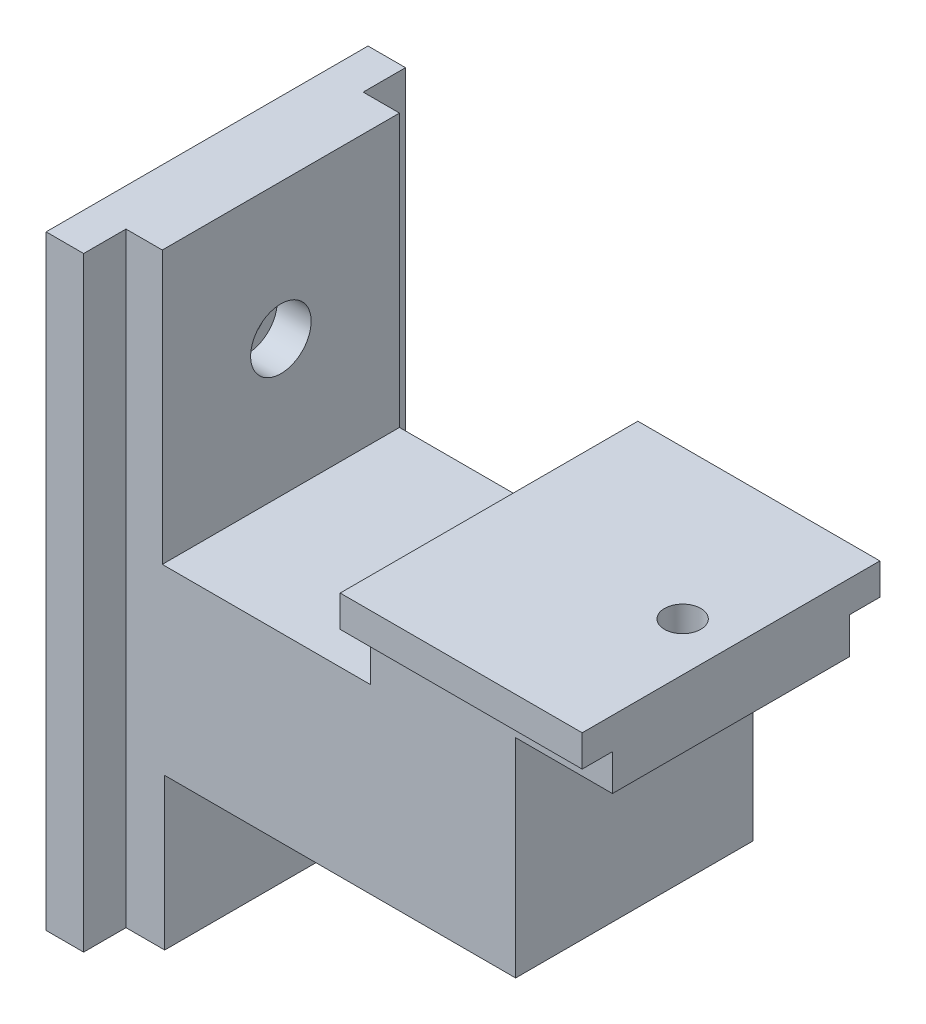
SolidWorks part; units mm, degrees
ref_plane "Front Plane" through (0, 0, 0) normal (0, 0, 1) x (1, 0, 0)
ref_plane "Top Plane" through (0, 0, 0) normal (0, 1, 0) x (1, 0, 0)
ref_plane "Right Plane" through (0, 0, 0) normal (1, 0, 0) x (0, 0, -1)
sketch "Sketch1" plane through (0, 0, 0) normal (0, 0, 1) x (1, 0, 0)
  line L0 (0, -7.5) -> (-32, -7.5)
  line L1 (-32, -7.5) -> (-32, 7.5)
  line L2 (-32, 7.5) -> (-12, 7.5)
  line L3 (-12, 7.5) -> (-12, 12.5)
  line L4 (-12, 12.5) -> (0, 12.5)
  line L5 (0, 12.5) -> (0, -7.5)
  point P8 (-32, 0)
  dimension "D1" = 15
  dimension "D2" = 20
  dimension "D3" = 12
  dimension "D4" = 20
extrude "Boss-Extrude1" add sketch "Sketch1" along normal mid plane 20
sketch "Sketch2" plane through (0, 0, 0) normal (0, 1, 0) x (1, 0, 0)
  line L0 (-32, 13.5) -> (-35.5, 13.5)
  line L1 (-35.5, 13.5) -> (-35.5, -13.5)
  line L2 (-35.5, -13.5) -> (-32, -13.5)
  line L3 (-32, -13.5) -> (-32, -10)
  line L5 (-32, 10) -> (-29, 10)
  line L6 (-12, 10) -> (-32, 10) construction
  line L7 (-29, 10) -> (-29, -10)
  line L8 (-12, -10) -> (-32, -10) construction
  line L9 (-29, -10) -> (-32, -10)
  line L10 (-32, 10) -> (-32, 13.5)
  line L11 (-32, 10) -> (-32, -10) construction
  point P11 (-35.5, 0)
  dimension "D1" = 3.5
  dimension "D2" = 27
  dimension "D3" = 3
extrude "Boss-Extrude2" add sketch "Sketch2" along normal blind 30 and the other way blind 20
sketch "Sketch3" plane through (0, 12.5, 0) normal (0, 1, 0) x (1, 0, 0)
  line L1 (8, -12.5) -> (-12, -12.5)
  line L2 (8, -12.5) -> (8, 12.5)
  line L3 (8, 12.5) -> (-12, 12.5)
  line L4 (-12, -12.5) -> (-12, 12.5)
  line L5 (8, -12.5) -> (-12, 12.5) construction
  line L6 (8, 12.5) -> (-12, -12.5) construction
  point P0 (-2, 0)
  dimension "D1" = 20
  dimension "D2" = 25
extrude "Boss-Extrude3" add sketch "Sketch3" along normal blind 3
sketch "Sketch4" plane through (0, 0, 0) normal (1, 0, 0) x (0, 0, -1)
  line L0 (-10, 12.5) -> (10, 12.5)
  line L1 (10, 12.5) -> (10, 9.5)
  line L2 (10, -7.5) -> (10, 12.5) construction
  line L3 (10, 9.5) -> (-10, 9.5)
  line L4 (-10, -7.5) -> (-10, 12.5) construction
  line L5 (-10, 9.5) -> (-10, 12.5)
  dimension "D1" = 3
extrude "Boss-Extrude4" add sketch "Sketch4" along normal up to surface (8 mm away) up to face at (8, 14, 0)
sketch "Sketch5" plane through (0, 9.5, 0) normal (0, -1, 0) x (1, 0, 0)
  line L0 (8, 10) -> (0, 10) construction
  line L1 (8, -10) -> (8, 10) construction
  circle A0 centre (4, 0) radius 1.5
  circle A1 centre (4, 0) radius 2.5
  point P6 (4, 10)
  dimension "D2" = 3
  dimension "D3" = 4
  dimension "D1" = 1
extrude "Cut-Extrude1" cut sketch "Sketch5" against normal through all contours A0 region at (4, 9.5, 0)
extrude "Cut-Extrude2" cut sketch "Sketch5<3>" against normal blind 2
sketch "Sketch5<3>" plane through (0, 9.5, 0) normal (0, -1, 0) x (1, 0, 0) same geometry as "Sketch5"
sketch "Sketch6" plane through (-29, 0, 0) normal (1, 0, 0) x (0, 0, -1)
  line L0 (-10, 7.5) -> (-10, 30) construction
  circle A0 centre (0, 18.75) radius 1.5
  circle A1 centre (0, 18.75) radius 2.5
  point P6 (-10, 18.75)
  dimension "D2" = 3
  dimension "D1" = 1
extrude "Cut-Extrude3" cut sketch "Sketch6" against normal up to surface (6.5 mm away) contours A0 region at (-29, 18.75, 0) up to face at (-35.5, 5, 0)
extrude "Cut-Extrude4" cut sketch "Sketch6<3>" against normal blind 3 contours A1 A0 region at (-29, 18.75, 2.4293)
sketch "Sketch6<3>" plane through (-29, 0, 0) normal (1, 0, 0) x (0, 0, -1) same geometry as "Sketch6"
other "Move Face1" flip direction yes face at (6.5, 9.5, 0) face at (-29, 18.75, -2.5) face at (-2, 12.5, -11.25) face at (-2, 14, -12.5) face at (2.5, 15.5, 0) face at (-2, 14, 12.5) face at (-2, 12.5, 11.25) face at (-33.75, 5, -13.5) face at (-32, 5, -11.75) face at (-15.6667, 5.3333, -10) face at (-35.5, 18.75, 1.5) face at (-15.6667, 5.3333, 10) face at (-32, 5, 11.75) face at (-33.75, 5, 13.5) offset 0.2 parameters "D1"=0.2
